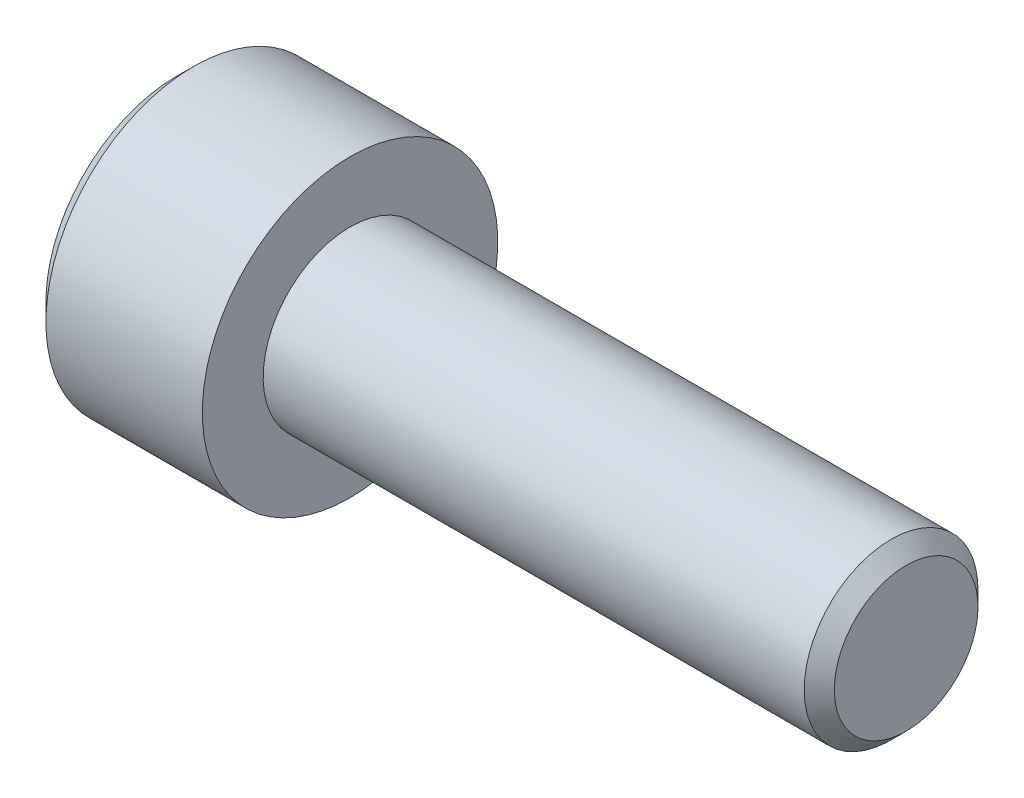
SolidWorks part; units mm, degrees
ref_plane "Front Plane" through (0, 0, 0) normal (0, 0, 1) x (1, 0, 0)
ref_plane "Top Plane" through (0, 0, 0) normal (0, 1, 0) x (1, 0, 0)
ref_plane "Right Plane" through (0, 0, 0) normal (1, 0, 0) x (0, 0, -1)
ref_axis "Axis_X" through (-6.05, 0, 0) along (1, 0, 0)
ref_axis "Axis_Y" through (0, 4.675, 0) along (0, -1, 0)
ref_axis "Axis_Z" through (0, 0, -4.675) along (0, 0, 1)
sketch "Sketch1" plane through (0, 0, 0) normal (0, 0, 1) x (1, 0, 0)
  line L0 (-4.1583, 0) -> (16, 0) construction
  line L1 (0, 2.5) -> (0, 4.25)
  line L2 (-5, 0) -> (-5, 3.75)
  line L3 (0, 2.5) -> (15.567, 2.5)
  line L4 (15.567, 2.5) -> (16, 2.067)
  line L5 (16, 2.067) -> (16, 0)
  line L6 (16, 0) -> (-5, 0)
  line L7 (-4.5, 4.25) -> (0, 4.25)
  line L8 (15.567, -2.5) -> (16, -2.067) construction
  line L9 (4.675, 0) -> (-4.675, 0) construction
  line L10 (-5, 3.75) -> (-4.5, 4.25)
  line L11 (-5, -3.75) -> (-4.5, -4.25) construction
  line L12 (0, -4.675) -> (0, 4.675) construction
  dimension "FIX_1" = 45
  dimension "M" = 5
  dimension "ATD_1" = 4.134
  dimension "L" = 16
  dimension "E" = 5
  dimension "A" = 8.5
revolve "Revolve1" add sketch "Sketch1" angle 360 about L6
sketch "Sketch2" plane through (-5, 0, 0) normal (-1, 0, 0) x (0, 0, 1)
  line L0 (0, -4.675) -> (0, 4.675) construction
  line L1 (0, 2.3094) -> (-2, 1.1547)
  line L2 (-2, 1.1547) -> (-2, -1.1547)
  line L3 (-2, -1.1547) -> (0, -2.3094)
  line L4 (0, -2.3094) -> (2, -1.1547)
  line L5 (2, -1.1547) -> (2, 1.1547)
  line L6 (2, 1.1547) -> (0, 2.3094)
  circle A0 centre (0, 0) radius 2 construction
  dimension "B" = 4
extrude "Cut-Extrude1" cut sketch "Sketch2" against normal blind 2.5
equation "\"Factor\"= 1.082532"
equation "\"Pitch\"= IIF ( \"M\" = 30 , 3.5 , IIF ( \"M\" = 24 , 3 , IIF ( \"M\" = 20 , 2.5 , IIF ( \"M\" = 16 , 2 , IIF ( \"M\" = 14 , 2 , IIF ( \"M\" = 12 , 1.75 , IIF ( \"M\" = 10 , 1.5 , IIF ( \"M\" = 8 , 1.25 , IIF ( \"M\" = 6 , 1 , IIF ( \"M\" = 5 , 0.8 , IIF ( \"M\" = 4 , 0.7 , IIF ( \"M\" = 3 , 0.5 , IIF ( \"M\" = 2.5 , 0.45 , 0.4 ) ) ) ) ) ) ) ) ) ) ) ) )"
equation "\"ATD_1\"= round ( \"M\" - \"Factor\" * \"Pitch\" , 3 )"
equation "\"L_s\"= IIF ( ( \"M\" = 12 and \"L\" > 50 ) , 36 , IIF ( ( \"M\" = 12 and \"L\" = < 50 ) , \"L\" , IIF ( ( \"M\" = 10 and \"L\" > 40 ) , 32 , IIF ( ( \"M\" = 10 and \"L\" = < 40 ) , \"L\" , IIF ( ( \"M\" = 8 and \"L\" > 35 ) , 28 , IIF ( ( \"M\" = 8 and \"L\" = < 35 ) , \"L\" , IIF ( ( \"M\" = 6 and \"L\" > 30 ) , 24 , IIF ( ( \"M\" = 6 and \"L\" = < 30 ) , \"L\" , IIF ( ( \"M\" = 5 and \"L\" > 25 ) , 22 , IIF ( ( \"M\" = 5 and \"L\" = < 25 ) , \"L\" , IIF ( ( \"M\" = 4 and \"L\" > 25 ) , 20 , IIF ( ( \"M\" = 4 and \"L\" = < 25 ) , \"L\" , IIF ( ( \"M\" = 3 and \"L\" > 20 ) , 18 , \"L\" ) ) ) ) ) ) ) ) ) ) ) ) )"
equation "\"E\"= \"M\""
equation "\"A\"= IIF ( \"M\" = 12 , 18 , IIF ( \"M\" = 10 , 16 , IIF ( \"M\" = 8 , 13 , IIF ( \"M\" = 6 , 10 , IIF ( \"M\" = 5 , 8.5 , IIF ( \"M\" = 4 , 7 , 5.5 ) ) ) ) ) )"
equation "\"B\"= IIF ( \"M\" = 12 , 10 , IIF ( \"M\" = 10 , 8 , IIF ( \"M\" = 8 , 6 , IIF ( \"M\" = 6 , 5 , IIF ( \"M\" = 5 , 4 , IIF ( \"M\" = 4 , 3 , 2.5 ) ) ) ) ) )"
equation "\"KSS_1\"= \"M\" / 10"
equation "\"KSS_2\"= \"M\" / 2"
